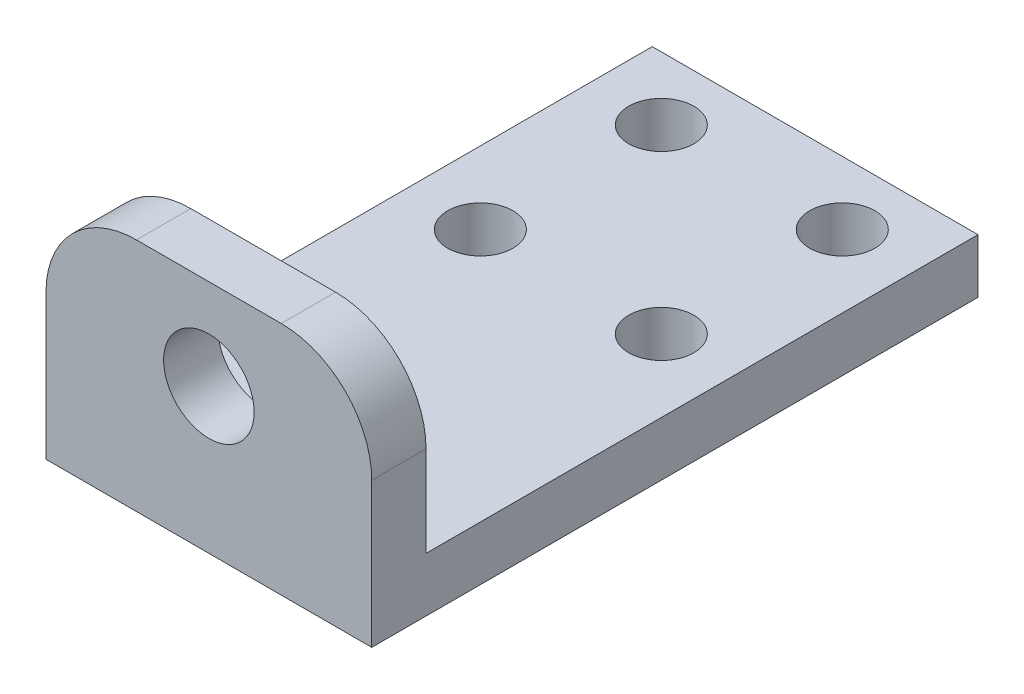
SolidWorks part; units mm, degrees
ref_plane "Front Plane" through (0, 0, 0) normal (0, 0, 1) x (1, 0, 0)
ref_plane "Top Plane" through (0, 0, 0) normal (0, 1, 0) x (1, 0, 0)
ref_plane "Right Plane" through (0, 0, 0) normal (1, 0, 0) x (0, 0, -1)
sketch "Sketch1" plane through (0, 0, 0) normal (1, 0, 0) x (0, 0, -1)
  line L0 (0, 0) -> (33.5, 0)
  line L1 (33.5, 0) -> (33.5, 3)
  line L2 (33.5, 3) -> (3, 3)
  line L3 (3, 3) -> (3, 13)
  line L4 (3, 13) -> (0, 13)
  line L5 (0, 13) -> (0, 0)
  dimension "D1" = 3
  dimension "D2" = 13
  dimension "D3" = 33.5
extrude "Boss-Extrude1" add sketch "Sketch1" along normal blind 18
sketch "Sketch2" plane through (0, 0, 0) normal (0, 0, 1) x (1, 0, 0)
  line L0 (0, 0) -> (18, 0) construction
  line L2 (9, 0) -> (9, 8) construction
  line L3 (18, 13) -> (0, 13) construction
  point P7 (9, 8)
  point P13 (9, 8)
  dimension "D1" = 5
hole_wizard "Ø5.0mm Dowel Hole1" positions "Sketch2" profile "Sketch3" hole size "Ø5.0" standard "ANSI Metric"
sketch "Sketch3" plane through (9, 8, 0) normal (1, 0, 0) x (0, -1, 0)
  line L0 (0, 0) -> (0, 4.5022)
  line L1 (0, 4.5022) -> (2.5, 3)
  line L2 (2.5, 3) -> (2.5, 0)
  line L5 (2.5, 0) -> (0, 0)
  line L10 (0, 4.5022) -> (-2.5, 3) construction
  line L11 (0, -6.35) -> (0, 107.95) construction
  dimension "Hole Dia." = 5
  dimension "Hole Depth" = 3
  dimension "Drill Angle" = 118
fillet "Fillet1" radius 5 2 edges at (0, 13, -1.5) (18, 13, -1.5)
sketch "Sketch4" plane through (0, 3, 0) normal (0, 1, 0) x (1, 0, 0)
  line L0 (9, 33.5) -> (9, 3) construction
  line L1 (18, 33.5) -> (0, 33.5) construction
  line L2 (18, 3) -> (0, 3) construction
  line L4 (18, 25) -> (0, 25) construction
  line L7 (0, 33.5) -> (0, 3) construction
  line L8 (18, 33.5) -> (18, 3) construction
  point P42 (4, 30)
  point P45 (4, 20)
  point P46 (14, 20)
  point P47 (14, 30)
  dimension "D1" = 5
  dimension "D2" = 5
  dimension "D3" = 8.5
hole_wizard "M3 Clearance Hole1" positions "Sketch4" profile "Sketch5" hole size "M3" standard "ANSI Metric" end condition through all
sketch "Sketch5" plane through (14, 3, -30) normal (1, 0, 0) x (0, 0, 1)
  line L0 (0, 0) -> (0, 3)
  line L1 (0, 3) -> (1.8, 3)
  line L2 (1.8, 3) -> (1.8, 0)
  line L5 (1.8, 0) -> (0, 0)
  line L11 (0, -6.35) -> (0, 107.95) construction
  dimension "Thru Hole Dia." = 3.6
  dimension "Thru Hole Depth" = 3
